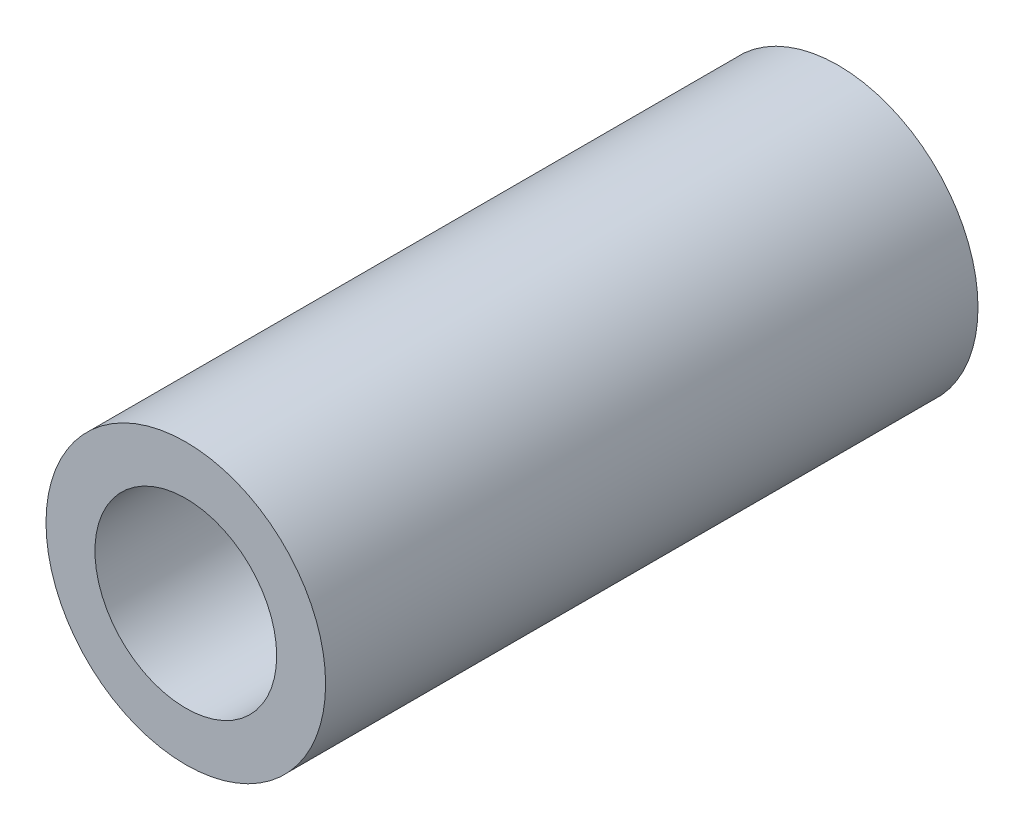
SolidWorks part; units mm, degrees
ref_plane "Plan de face" through (0, 0, 0) normal (1, 0, 0) x (0, 1, 0)
ref_plane "Plan de dessus" through (0, 0, 0) normal (0, 0, 1) x (0, 1, 0)
ref_plane "Plan de droite" through (0, 0, 0) normal (0, 1, 0) x (-1, 0, 0)
sketch "Esquisse1" plane through (0, 0, 0) normal (0, 0, 1) x (0, 1, 0)
  circle A0 centre (0, 0) radius 7.5
  dimension "D1" = 15
extrude "Boss.-Extru.1" add sketch "Esquisse1" along normal blind 35
sketch "Esquisse2" plane through (0, 0, 35) normal (0, 0, 1) x (1, 0, 0)
  circle A0 centre (0, 0) radius 4.875
  dimension "D1" = 9.75
extrude "Enlèv. mat.-Extru.1" cut sketch "Esquisse2" against normal blind 16
sketch "Esquisse3" plane through (0, 0, 0) normal (0, 0, -1) x (1, 0, 0)
  circle A0 centre (0, 0) radius 4.025
  dimension "D1" = 8.05
extrude "Enlèv. mat.-Extru.2" cut sketch "Esquisse3" against normal blind 16
sketch "Esquisse5" plane through (0, 0, 16) normal (0, 0, -1) x (1, 0, 0)
  line L0 (-2.8046, 2.887) -> (3.1531, 2.5018)
  arc A0 (-2.8046, 2.887) -> (3.1531, 2.5018) centre (0, 0) cw
  circle A1 centre (0, 0) radius 4.025 construction
  dimension "D1" = 2.7
extrude "Boss.-Extru.3" add sketch "Esquisse5" along normal blind 9
